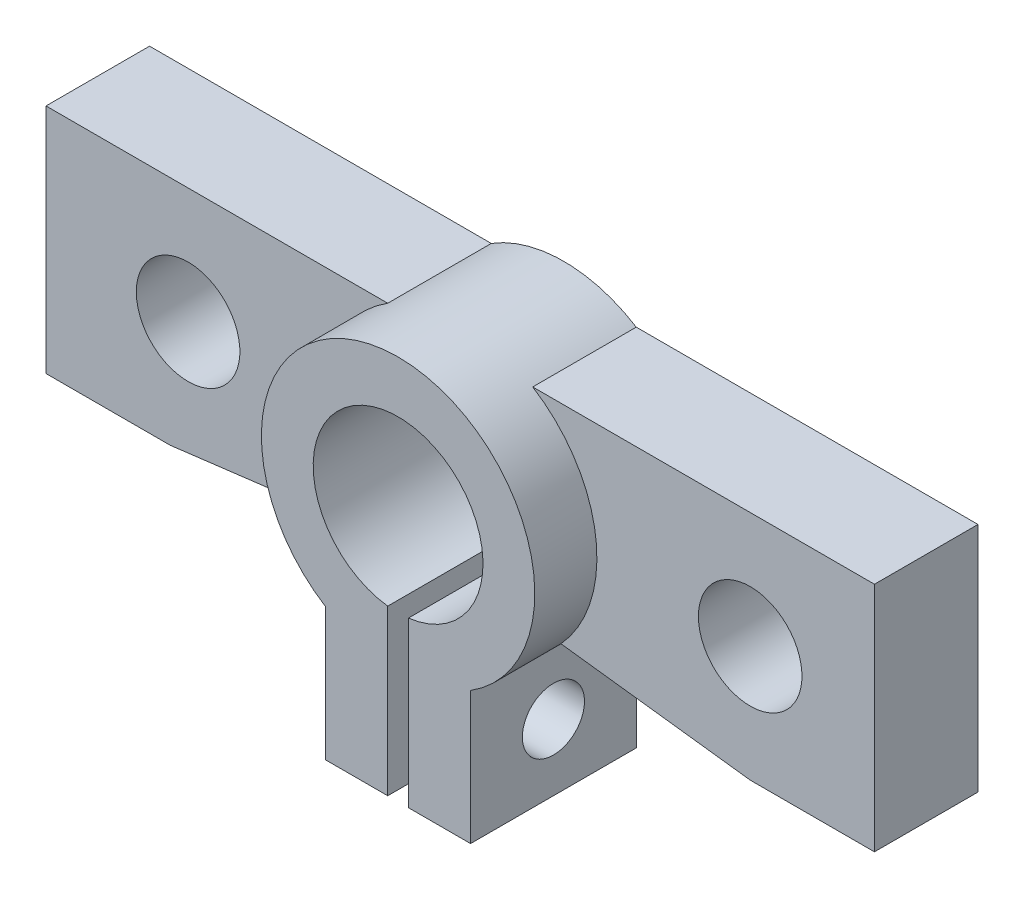
SolidWorks part; units mm, degrees
material "ABS"
ref_plane "Front Plane" through (0, 0, 0) normal (1, 0, 0) x (0, 1, 0)
ref_plane "Top Plane" through (0, 0, 0) normal (0, 0, 1) x (0, 1, 0)
ref_plane "Right Plane" through (0, 0, 0) normal (0, 1, 0) x (-1, 0, 0)
sketch "Sketch1" plane through (0, 0, 0) normal (0, 0, 1) x (0, 1, 0)
  line L0 (-12, 3.5) -> (-5.5955, 3.5)
  line L5 (-12, 3.5) -> (-12, 0.5)
  line L6 (-12, 0.5) -> (-4.0694, 0.5)
  line L7 (-12, -0.5) -> (-4.0694, -0.5)
  line L8 (-12, -0.5) -> (-12, -3.5)
  line L9 (-12, -3.5) -> (-5.5955, -3.5)
  line L10 (1000, 0) -> (4.1, 0) construction
  line L11 (-4.1, 0) -> (-6.6, 0) construction
  line L12 (-6.6, 0) -> (-1015.8416, 0) construction
  line L13 (4.1, 0) -> (-4.1, 0) construction
  arc A0 (-5.5955, -3.5) -> (-5.5955, 3.5) centre (0, 0) ccw
  arc A1 (-4.0694, -0.5) -> (-4.0694, 0.5) centre (0, 0) ccw
  arc A2 (-6.581, 0.5) -> (-6.6, 0) centre (0, 0) ccw construction
  arc A3 (-6.6, 0) -> (-6.581, -0.5) centre (0, 0) ccw construction
  arc A4 (-5.5955, 3.5) -> (-6.581, 0.5) centre (0, 0) ccw construction
  arc A5 (-6.581, -0.5) -> (-5.5955, -3.5) centre (0, 0) ccw construction
  arc A6 (-4.1, 0) -> (-4.0694, -0.5) centre (0, 0) ccw construction
  arc A7 (-4.0694, 0.5) -> (-4.1, 0) centre (0, 0) ccw construction
  point P752 (0, 0)
  dimension "D1" = 8.2
  dimension "D2" = 13.2
  dimension "D3" = 3
  dimension "D4" = 3
  dimension "D5" = 0.5
  dimension "D6" = 0.5
  dimension "D7" = 12
extrude "Boss-Extrude1" add sketch "Sketch1" along normal blind 8
sketch "Sketch2" plane through (-3.5, 0, 0) normal (-1, 0, 0) x (0, -1, 0)
  line L0 (8.7978, 8) -> (8.7978, 0) construction
  line L1 (5.5955, 8) -> (12, 8) construction
  line L2 (5.5955, 0) -> (12, 0) construction
  circle A0 centre (8.7978, 4) radius 1.5
  dimension "D1" = 3
extrude "Cut-Extrude1" cut sketch "Sketch2" against normal blind 8 contours L0 A0 | A0 L0 region at (-3.5, -9.4344, 4) region at (-3.5, -8.1611, 4)
sketch "Sketch4" plane through (0, 0, 0) normal (0, 0, -1) x (1, 0, 0)
  line L0 (0.6849, 0) -> (10.7733, 0) construction
  line L1 (14, 5.5955) -> (20, 5.5955)
  line L2 (20, 5.5955) -> (20, -5.5955)
  line L3 (20, -5.5955) -> (3.5, -5.5955)
  line L4 (14, 5.5955) -> (4.863, 4.4622)
  line L5 (3.5, 5.5955) -> (14, 5.5955) construction
  line L6 (-3.5, -5.5955) -> (-20, -5.5955)
  line L7 (-20, -5.5955) -> (-20, 5.5955)
  line L8 (-20, 5.5955) -> (-14, 5.5955)
  line L9 (-4.863, 4.4622) -> (-14, 5.5955)
  line L10 (-14, 5.5955) -> (-3.5, 5.5955) construction
  arc A0 (-3.5, 5.5955) -> (3.5, 5.5955) centre (0, 0) ccw construction
  circle A1 centre (14, 0) radius 2.5
  circle A2 centre (-13.1394, 0) radius 2.5
  arc M7 (-3.5, 5.5955) -> (3.5, 5.5955) centre (0, 0) ccw
  dimension "D4" = 5
  dimension "D1" = 20
  dimension "D2" = 20
  dimension "D3" = 6
extrude "Boss-Extrude2" add sketch "Sketch4" against normal blind 5 contours L1 L4 L3 L2 A1 M7 | L9 L8 L7 L6 A2 M7 region at (-11.75, 5.3962, 0) region at (17, -5.3962, 0)
equation "\"D2@Sketch1\"=\"D1@Sketch1\"+5"
equation "\"extrusion_width\"= 20mm"
equation "\"frame_height\"= 360mm"
equation "\"frame_width\"= 320mm"
equation "\"frame_length\"= 320mm"
equation "\"bed_radius\"= 100mm"
equation "\"D4@Sketch1\"=\"D3@Sketch1\""
equation "\"D6@Sketch1\"=\"D5@Sketch1\""
equation "\"D2@Sketch4\"=\"D1@Sketch4\""
equation "\"hole_for_extrusion_mounting\"= 5mm"
equation "\"cantilever_support_thickness\"= 5mm"
equation "\"D4@Sketch4\"=\"hole_for_extrusion_mounting\""
